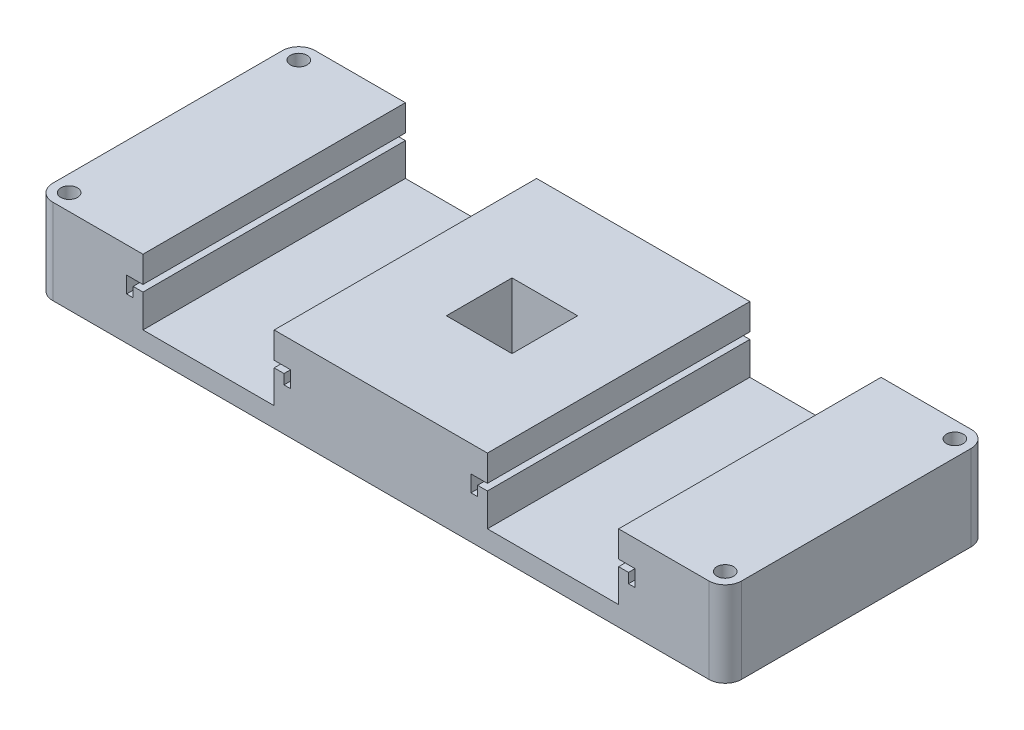
SolidWorks part; units mm, degrees
ref_plane "Front Plane" through (0, 0, 0) normal (0, 0, 1) x (1, 0, 0)
ref_plane "Top Plane" through (0, 0, 0) normal (0, 1, 0) x (1, 0, 0)
ref_plane "Right Plane" through (0, 0, 0) normal (1, 0, 0) x (0, 0, -1)
sketch "Sketch1" plane through (0, 0, 0) normal (0, 1, 0) x (1, 0, 0)
  line L1 (5, 0) -> (205, 0)
  line L2 (0, 5) -> (0, 75)
  line L3 (5, 80) -> (205, 80)
  line L4 (210, 5) -> (210, 75)
  arc A0 (210, 75) -> (205, 80) centre (205, 75) ccw
  arc A1 (210, 5) -> (205, 0) centre (205, 5) cw
  arc A2 (5, 0) -> (0, 5) centre (5, 5) cw
  arc A3 (5, 80) -> (0, 75) centre (5, 75) ccw
  point P7 (210, 80)
  point P10 (210, 0)
  point P13 (0, 0)
  dimension "D3" = 5
  dimension "D1" = 210
  dimension "D2" = 80
extrude "Boss-Extrude1" add sketch "Sketch1" along normal blind 26
sketch "Sketch2" plane through (0, 0, 0) normal (0, 0, 1) x (1, 0, 0)
  line L0 (52.5, 64.5271) -> (52.5, -47.3665) construction
  line L1 (157.5, -47.3665) -> (157.5, 64.5271) construction
  line L2 (0, 26) -> (0, 0) construction
  line L3 (210, 26) -> (210, 0) construction
  line L4 (5, 26) -> (205, 26) construction
  line L5 (32.5, 26) -> (72.5, 26)
  line L6 (32.5, 26) -> (32.5, 6)
  line L7 (32.5, 6) -> (72.5, 6)
  line L8 (72.5, 26) -> (72.5, 6)
  line L10 (137.5, 26) -> (177.5, 26)
  line L11 (137.5, 26) -> (137.5, 6)
  line L12 (137.5, 6) -> (177.5, 6)
  line L13 (177.5, 26) -> (177.5, 6)
  point P14 (52.5, 26)
  point P19 (157.5, 26)
  dimension "D1" = 52.5
  dimension "D2" = 52.5
  dimension "D3" = 20
  dimension "D4" = 40
  dimension "D5" = 20
  dimension "D6" = 40
extrude "Cut-Extrude1" cut sketch "Sketch2" against normal through all
hole_wizard "1/4-20 Tapped Hole1" positions "3DSketch1" profile "Sketch3" tap size "1/4-20" standard "ANSI Inch" end condition through all
sketch3d "3DSketch1"
  line L0 (32.5, 26, -80) -> (5, 26, -80) construction
  line L1 (0, 26, -75) -> (0, 26, -5) construction
  line L2 (177.5, 26, 0) -> (205, 26, 0) construction
  line L3 (210, 26, -5) -> (210, 26, -75) construction
  line L4 (5, 26, 0) -> (32.5, 26, 0) construction
  line L5 (205, 26, -80) -> (177.5, 26, -80) construction
  point P2 (5, 26, -75)
  point P4 (5, 26, -5)
  point P6 (205, 26, -5)
  point P8 (205, 26, -75)
  point P11 (0, 0, 0)
  dimension "D1" = 5
  dimension "D2" = 5
  dimension "D3" = 5
  dimension "D4" = 5
  dimension "D5" = 5
  dimension "D6" = 5
  dimension "D7" = 5
  dimension "D8" = 5
sketch "Sketch3" plane through (5, 26, -75) normal (1, 0, 0) x (0, 0, 1)
  line L0 (0, 0) -> (0, 26)
  line L1 (0, 26) -> (2.5527, 26)
  line L2 (2.5527, 26) -> (2.5527, 0)
  line L5 (2.5527, 0) -> (0, 0)
  line L11 (0, -6.35) -> (0, 107.95) construction
  dimension "Thru Tap Drill Dia." = 5.1054
  dimension "Thru Tap Drill Depth" = 26
cosmetic thread "Hole Thread1" parameters "D2"=6.35
cosmetic thread "Hole Thread2" parameters "D2"=6.35
cosmetic thread "Hole Thread3" parameters "D2"=6.35
cosmetic thread "Hole Thread4" parameters "D2"=6.35
sketch "Sketch4" plane through (0, 26, 0) normal (0, 1, 0) x (1, 0, 0)
  line L0 (0, 0) -> (0, 40) construction
  line L1 (95, 50) -> (115, 50)
  line L2 (95, 50) -> (95, 30)
  line L3 (95, 30) -> (115, 30)
  line L4 (115, 50) -> (115, 30)
  line L5 (0, 75) -> (0, 5) construction
  line L6 (0, 0) -> (105, 0) construction
  line L7 (72.5, 0) -> (137.5, 0) construction
  point P9 (105, 30)
  point P10 (95, 40)
  dimension "D1" = 20
  dimension "D2" = 20
extrude "Cut-Extrude2" cut sketch "Sketch4" against normal through all
sketch "Sketch5" plane through (0, 0, 0) normal (0, 0, 1) x (1, 0, 0)
  line L1 (52.5, 6) -> (52.5, 38.4877) construction
  line L9 (32.5, 18) -> (27.5, 18)
  line L10 (32.5, 26) -> (32.5, 6) construction
  line L11 (27.5, 18) -> (27.5, 13)
  line L12 (27.5, 13) -> (29.5, 13)
  line L13 (29.5, 13) -> (29.5, 16)
  line L14 (29.5, 16) -> (32.5, 16)
  line L15 (32.5, 16) -> (32.5, 18)
  line L16 (5, 26) -> (32.5, 26) construction
  line L18 (32.5, 6) -> (72.5, 6) construction
  line L19 (75.5, 16) -> (72.5, 16)
  line L20 (75.5, 13) -> (75.5, 16)
  line L21 (77.5, 13) -> (75.5, 13)
  line L22 (77.5, 18) -> (77.5, 13)
  line L23 (72.5, 18) -> (77.5, 18)
  line L24 (72.5, 16) -> (72.5, 18)
  line L25 (105, 0) -> (105, 44.8657) construction
  line L27 (5, 0) -> (205, 0) construction
  line L28 (134.5, 13) -> (134.5, 16)
  line L29 (132.5, 13) -> (134.5, 13)
  line L30 (132.5, 18) -> (132.5, 13)
  line L31 (137.5, 18) -> (132.5, 18)
  line L32 (137.5, 16) -> (137.5, 18)
  line L33 (134.5, 16) -> (137.5, 16)
  line L34 (180.5, 16) -> (177.5, 16)
  line L35 (180.5, 13) -> (180.5, 16)
  line L36 (182.5, 13) -> (180.5, 13)
  line L37 (182.5, 18) -> (182.5, 13)
  line L38 (177.5, 18) -> (182.5, 18)
  line L39 (177.5, 16) -> (177.5, 18)
  point P11 (52.5, 22.2439)
  point P15 (52.5, 6)
  point P23 (105, 22.4329)
  point P27 (105, 0)
  dimension "D1" = 5
  dimension "D2" = 3
  dimension "D3" = 5
  dimension "D4" = 8
  dimension "D5" = 2
extrude "Cut-Extrude3" cut sketch "Sketch5" against normal through all
